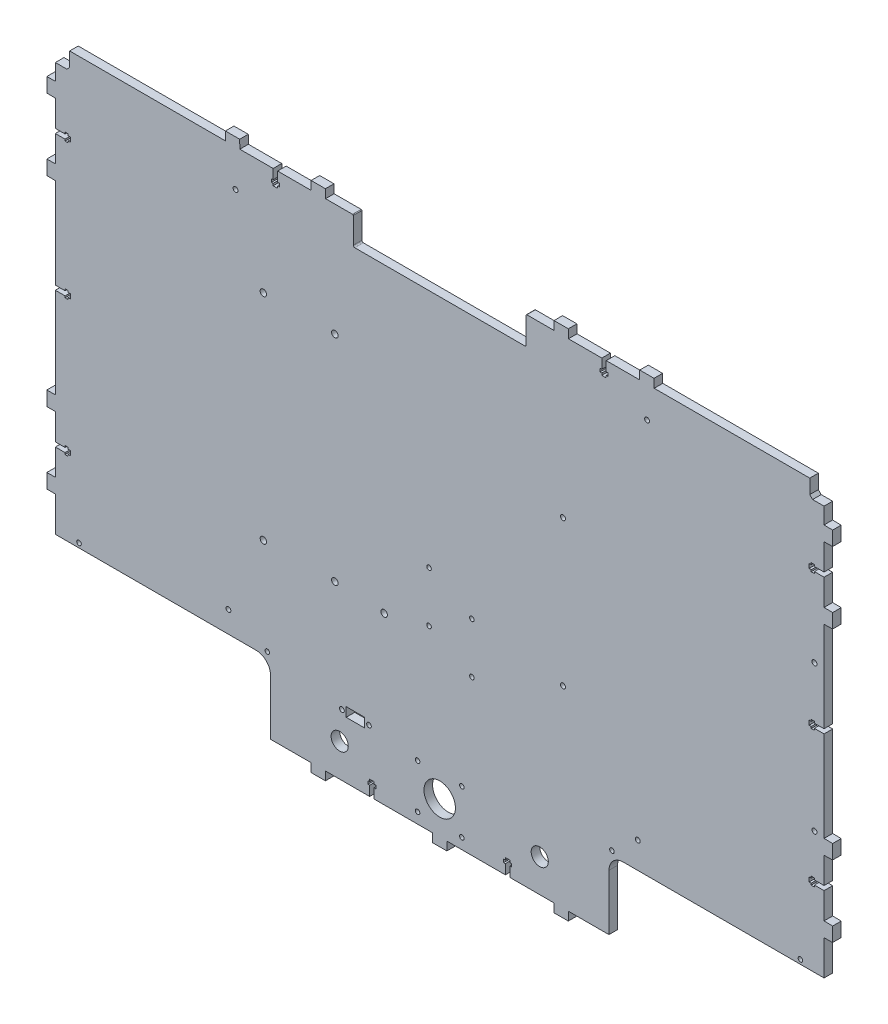
SolidWorks part; units mm, degrees
material "Клен"
ref_plane "Front" through (0, 0, 0) normal (0, 0, 1) x (1, 0, 0)
ref_plane "Top" through (0, 0, 0) normal (0, 1, 0) x (1, 0, 0)
ref_plane "Right" through (0, 0, 0) normal (1, 0, 0) x (0, 0, -1)
sketch "Эскиз1" plane through (0, 0, 0) normal (0, 0, 1) x (1, 0, 0)
  line L0 (89.7419, 501.6876) -> (118.0919, 501.6876)
  line L1 (118.0919, 501.6876) -> (118.1919, 495.6876)
  line L2 (118.1919, 495.6876) -> (128.1919, 495.6876)
  line L3 (128.1919, 495.6876) -> (128.2919, 501.6876)
  line L4 (128.2919, 501.6876) -> (159.1419, 501.6876)
  line L5 (159.1419, 501.6876) -> (159.1419, 508.4876)
  line L6 (159.1419, 508.4876) -> (157.9419, 508.4876)
  line L7 (157.9419, 508.4876) -> (157.9419, 510.6876)
  line L8 (157.9419, 510.6876) -> (159.1419, 510.6876)
  line L9 (159.1419, 510.6876) -> (159.1419, 512.1876)
  line L10 (159.1419, 512.1876) -> (162.2419, 512.1876)
  line L11 (162.2419, 512.1876) -> (162.2419, 510.6876)
  line L12 (162.2419, 510.6876) -> (163.4419, 510.6876)
  line L13 (163.4419, 510.6876) -> (163.4419, 508.4876)
  line L14 (163.4419, 508.4876) -> (162.2419, 508.4876)
  line L15 (162.2419, 508.4876) -> (162.2419, 501.6876)
  line L16 (-51.8081, 697.342) -> (-54.0081, 697.342)
  line L17 (-66.8081, 625.092) -> (-60.8081, 624.992)
  line L18 (162.2419, 501.6876) -> (203.0919, 501.6876)
  line L19 (203.0919, 501.6876) -> (203.1919, 495.6876)
  line L20 (203.1919, 495.6876) -> (213.1919, 495.6876)
  line L21 (213.1919, 495.6876) -> (213.2919, 501.6876)
  line L22 (213.2919, 501.6876) -> (254.1419, 501.6876)
  line L23 (254.1419, 501.6876) -> (254.1419, 508.4876)
  line L24 (254.1419, 508.4876) -> (252.9419, 508.4876)
  line L25 (252.9419, 508.4876) -> (252.9419, 510.6876)
  line L26 (252.9419, 510.6876) -> (254.1419, 510.6876)
  line L27 (254.1419, 510.6876) -> (254.1419, 512.1876)
  line L28 (254.1419, 512.1876) -> (257.2419, 512.1876)
  line L29 (257.2419, 512.1876) -> (257.2419, 510.6876)
  line L30 (257.2419, 510.6876) -> (258.4419, 510.6876)
  line L31 (258.4419, 510.6876) -> (258.4419, 508.4876)
  line L32 (258.4419, 508.4876) -> (257.2419, 508.4876)
  line L33 (257.2419, 508.4876) -> (257.2419, 501.6876)
  line L34 (257.2419, 501.6876) -> (288.0919, 501.6876)
  line L35 (288.0919, 501.6876) -> (288.1919, 495.6876)
  line L36 (288.1919, 495.6876) -> (298.1919, 495.6876)
  line L37 (298.1919, 495.6876) -> (298.2919, 501.6876)
  line L38 (298.2919, 501.6876) -> (326.6419, 501.6876)
  line L97 (367.1919, 848.6876) -> (358.2919, 848.6876)
  line L98 (358.2919, 848.6876) -> (358.1919, 854.6876)
  line L99 (358.1919, 854.6876) -> (348.1919, 854.6876)
  line L100 (348.1919, 854.6876) -> (348.0919, 848.6876)
  line L101 (348.0919, 848.6876) -> (324.7419, 848.6876)
  line L102 (324.7419, 848.6876) -> (324.7419, 841.8876)
  line L103 (324.7419, 841.8876) -> (325.9419, 841.8876)
  line L104 (325.9419, 841.8876) -> (325.9419, 839.6876)
  line L105 (325.9419, 839.6876) -> (324.7419, 839.6876)
  line L106 (324.7419, 839.6876) -> (324.7419, 838.1876)
  line L107 (324.7419, 838.1876) -> (321.6419, 838.1876)
  line L108 (321.6419, 838.1876) -> (321.6419, 839.6876)
  line L109 (321.6419, 839.6876) -> (320.4419, 839.6876)
  line L110 (320.4419, 839.6876) -> (320.4419, 841.8876)
  line L111 (320.4419, 841.8876) -> (321.6419, 841.8876)
  line L112 (321.6419, 841.8876) -> (321.6419, 848.6876)
  line L113 (321.6419, 848.6876) -> (298.2919, 848.6876)
  line L114 (298.2919, 848.6876) -> (298.1919, 854.6876)
  line L115 (298.1919, 854.6876) -> (288.1919, 854.6876)
  line L116 (288.1919, 854.6876) -> (288.0919, 848.6876)
  line L117 (288.0919, 848.6876) -> (269.1919, 848.6876)
  line L118 (268.6919, 848.1876) -> (268.6919, 830.092)
  line L119 (267.6919, 829.092) -> (148.6919, 829.092)
  line L120 (147.6919, 830.092) -> (147.6919, 848.092)
  line L121 (147.1919, 848.592) -> (128.2919, 848.592)
  line L122 (128.2919, 848.592) -> (128.1919, 854.592)
  line L123 (128.1919, 854.592) -> (118.1919, 854.592)
  line L124 (118.1919, 854.592) -> (118.0919, 848.592)
  line L125 (118.0919, 848.592) -> (94.7419, 848.592)
  line L126 (94.7419, 848.592) -> (94.7419, 841.792)
  line L127 (94.7419, 841.792) -> (95.9419, 841.792)
  line L128 (95.9419, 841.792) -> (95.9419, 839.592)
  line L129 (95.9419, 839.592) -> (94.7419, 839.592)
  line L130 (94.7419, 839.592) -> (94.7419, 838.092)
  line L131 (94.7419, 838.092) -> (91.6419, 838.092)
  line L132 (91.6419, 838.092) -> (91.6419, 839.592)
  line L133 (91.6419, 839.592) -> (90.4419, 839.592)
  line L134 (90.4419, 839.592) -> (90.4419, 841.792)
  line L135 (90.4419, 841.792) -> (91.6419, 841.792)
  line L136 (91.6419, 841.792) -> (91.6419, 848.592)
  line L137 (91.6419, 848.592) -> (68.2919, 848.592)
  line L138 (68.2919, 848.592) -> (68.1919, 854.592)
  line L139 (68.1919, 854.592) -> (58.1919, 854.592)
  line L140 (58.1919, 854.592) -> (58.0919, 848.592)
  line L141 (58.0919, 848.592) -> (49.1919, 848.592)
  line L199 (39.1919, 871.432) -> (39.1919, 501.6876) construction
  line L201 (142.7002, 547.9475) -> (155.7002, 547.9475)
  line L202 (155.7002, 547.9475) -> (155.7002, 541.4475)
  line L203 (155.7002, 541.4475) -> (142.7002, 541.4475)
  line L204 (142.7002, 541.4475) -> (142.7002, 547.9475)
  line L205 (-60.8081, 871.432) -> (-60.8081, 501.6876) construction
  line L206 (-50.3081, 793.542) -> (-51.8081, 793.542)
  line L207 (-60.8081, 698.542) -> (-60.8081, 635.192)
  line L208 (-60.8081, 796.642) -> (-54.0081, 796.642)
  line L209 (-51.8081, 793.542) -> (-51.8081, 792.342)
  line L210 (-54.0081, 701.642) -> (-54.0081, 702.842)
  line L211 (-51.8081, 701.642) -> (-50.3081, 701.642)
  line L212 (-60.8081, 836.592) -> (-60.8081, 825.192)
  line L213 (-51.8081, 796.642) -> (-50.3081, 796.642)
  line L214 (-54.0081, 702.842) -> (-51.8081, 702.842)
  line L215 (-50.3081, 698.542) -> (-51.8081, 698.542)
  line L216 (-54.0081, 603.542) -> (-60.8081, 603.542)
  line L217 (-60.8081, 775.192) -> (-66.8081, 775.092)
  line L218 (-50.3081, 603.542) -> (-51.8081, 603.542)
  line L219 (-60.8081, 814.992) -> (-60.8081, 796.642)
  line L220 (-54.0081, 796.642) -> (-54.0081, 797.842)
  line L221 (-54.0081, 797.842) -> (-51.8081, 797.842)
  line L222 (-51.8081, 698.542) -> (-51.8081, 697.342)
  line L223 (-54.0081, 607.842) -> (-51.8081, 607.842)
  line L224 (-60.8081, 574.992) -> (-60.8081, 550.592)
  line L225 (-52.8081, 836.592) -> (-60.8081, 836.592)
  line L226 (-54.0081, 792.342) -> (-54.0081, 793.542)
  line L227 (-51.8081, 606.642) -> (-50.3081, 606.642)
  line L228 (-66.8081, 585.092) -> (-66.8081, 575.092)
  line L229 (-51.8081, 792.342) -> (-54.0081, 792.342)
  line L230 (-54.0081, 606.642) -> (-54.0081, 607.842)
  line L231 (-51.8081, 603.542) -> (-51.8081, 602.342)
  line L232 (-66.8081, 825.092) -> (-66.8081, 815.092)
  line L233 (-50.3081, 796.642) -> (-50.3081, 793.542)
  line L234 (-60.8081, 635.192) -> (-66.8081, 635.092)
  line L235 (-60.8081, 585.192) -> (-66.8081, 585.092)
  line L236 (-66.8081, 815.092) -> (-60.8081, 814.992)
  line L237 (-66.8081, 775.092) -> (-66.8081, 765.092)
  line L238 (-51.8081, 602.342) -> (-54.0081, 602.342)
  line L239 (-66.8081, 765.092) -> (-60.8081, 764.992)
  line L240 (-50.3081, 701.642) -> (-50.3081, 698.542)
  line L241 (-60.8081, 624.992) -> (-60.8081, 606.642)
  line L243 (-54.0081, 793.542) -> (-60.8081, 793.542)
  line L244 (-54.0081, 697.342) -> (-54.0081, 698.542)
  line L245 (-60.8081, 825.192) -> (-66.8081, 825.092)
  line L246 (-51.8081, 797.842) -> (-51.8081, 796.642)
  line L247 (-51.8081, 702.842) -> (-51.8081, 701.642)
  line L248 (-60.8081, 603.542) -> (-60.8081, 585.192)
  line L249 (-54.0081, 698.542) -> (-60.8081, 698.542)
  line L250 (-66.8081, 635.092) -> (-66.8081, 625.092)
  line L251 (-60.8081, 764.992) -> (-60.8081, 701.642)
  line L252 (-54.0081, 602.342) -> (-54.0081, 603.542)
  line L254 (-50.8081, 848.592) -> (-50.8081, 838.592)
  line L255 (-50.8081, 838.592) -> (-52.8081, 836.592)
  line L256 (-60.8081, 701.642) -> (-54.0081, 701.642)
  line L257 (-60.8081, 606.642) -> (-54.0081, 606.642)
  line L258 (-50.3081, 606.642) -> (-50.3081, 603.542)
  line L259 (-60.8081, 793.542) -> (-60.8081, 775.192)
  line L260 (-51.8081, 607.842) -> (-51.8081, 606.642)
  line L261 (-66.8081, 575.092) -> (-60.8081, 574.992)
  line L263 (-50.8081, 848.592) -> (49.1919, 848.592)
  line L264 (377.1919, 871.432) -> (377.1919, 476.2445) construction
  line L265 (477.1919, 871.432) -> (477.1919, 476.2445) construction
  line L266 (477.1919, 625.0876) -> (483.1919, 625.1876)
  line L267 (466.6919, 698.6376) -> (466.6919, 701.7376)
  line L268 (477.1919, 550.6876) -> (477.1919, 575.0876)
  line L269 (470.3919, 701.7376) -> (477.1919, 701.7376)
  line L270 (477.1919, 585.2876) -> (477.1919, 603.6376)
  line L271 (477.1919, 796.7376) -> (477.1919, 815.0876)
  line L272 (477.1919, 575.0876) -> (483.1919, 575.1876)
  line L273 (468.1919, 603.6376) -> (466.6919, 603.6376)
  line L274 (477.1919, 635.2876) -> (477.1919, 698.6376)
  line L275 (470.3919, 792.4376) -> (468.1919, 792.4376)
  line L276 (467.1919, 838.6876) -> (467.1919, 848.6876)
  line L277 (483.1919, 635.1876) -> (477.1919, 635.2876)
  line L278 (468.1919, 796.7376) -> (468.1919, 797.9376)
  line L279 (483.1919, 585.1876) -> (477.1919, 585.2876)
  line L280 (468.1919, 698.6376) -> (466.6919, 698.6376)
  line L281 (468.1919, 793.6376) -> (466.6919, 793.6376)
  line L282 (469.1919, 836.6876) -> (467.1919, 838.6876)
  line L283 (483.1919, 575.1876) -> (483.1919, 585.1876)
  line L284 (470.3919, 603.6376) -> (470.3919, 602.4376)
  line L285 (470.3919, 697.4376) -> (468.1919, 697.4376)
  line L286 (477.1919, 701.7376) -> (477.1919, 765.0876)
  line L287 (477.1919, 793.6376) -> (470.3919, 793.6376)
  line L288 (483.1919, 815.1876) -> (483.1919, 825.1876)
  line L289 (470.3919, 606.7376) -> (477.1919, 606.7376)
  line L290 (470.3919, 698.6376) -> (470.3919, 697.4376)
  line L291 (483.1919, 775.1876) -> (477.1919, 775.2876)
  line L292 (466.6919, 603.6376) -> (466.6919, 606.7376)
  line L293 (466.6919, 793.6376) -> (466.6919, 796.7376)
  line L294 (470.3919, 797.9376) -> (470.3919, 796.7376)
  line L295 (477.1919, 825.2876) -> (477.1919, 836.6876)
  line L296 (470.3919, 602.4376) -> (468.1919, 602.4376)
  line L297 (483.1919, 625.1876) -> (483.1919, 635.1876)
  line L298 (468.1919, 697.4376) -> (468.1919, 698.6376)
  line L299 (470.3919, 702.9376) -> (470.3919, 701.7376)
  line L301 (468.1919, 607.9376) -> (470.3919, 607.9376)
  line L302 (470.3919, 793.6376) -> (470.3919, 792.4376)
  line L303 (466.6919, 796.7376) -> (468.1919, 796.7376)
  line L304 (477.1919, 603.6376) -> (470.3919, 603.6376)
  line L305 (477.1919, 606.7376) -> (477.1919, 625.0876)
  line L306 (477.1919, 775.2876) -> (477.1919, 793.6376)
  line L307 (468.1919, 792.4376) -> (468.1919, 793.6376)
  line L308 (477.1919, 815.0876) -> (483.1919, 815.1876)
  line L309 (466.6919, 606.7376) -> (468.1919, 606.7376)
  line L310 (468.1919, 606.7376) -> (468.1919, 607.9376)
  line L311 (466.6919, 701.7376) -> (468.1919, 701.7376)
  line L312 (468.1919, 702.9376) -> (470.3919, 702.9376)
  line L313 (468.1919, 797.9376) -> (470.3919, 797.9376)
  line L315 (470.3919, 607.9376) -> (470.3919, 606.7376)
  line L316 (477.1919, 698.6376) -> (470.3919, 698.6376)
  line L317 (468.1919, 701.7376) -> (468.1919, 702.9376)
  line L318 (477.1919, 765.0876) -> (483.1919, 765.1876)
  line L319 (470.3919, 796.7376) -> (477.1919, 796.7376)
  line L320 (468.1919, 602.4376) -> (468.1919, 603.6376)
  line L321 (483.1919, 765.1876) -> (483.1919, 775.1876)
  line L322 (483.1919, 825.1876) -> (477.1919, 825.2876)
  line L323 (477.1919, 836.6876) -> (469.1919, 836.6876)
  line L325 (367.1919, 848.6876) -> (467.1919, 848.6876)
  line L326 (336.6419, 550.6876) -> (377.1919, 550.6876)
  line L327 (326.6419, 501.6876) -> (326.6419, 540.6876)
  line L328 (377.1919, 550.6876) -> (477.1919, 550.6876)
  line L329 (89.7419, 540.592) -> (89.7419, 501.6876)
  line L330 (79.7419, 550.592) -> (39.1919, 550.592)
  line L331 (-60.8081, 550.592) -> (39.1919, 550.592)
  line L332 (208.1919, 486.1481) -> (208.1919, 880.8098) construction
  line L333 (107.749, 553.6876) -> (-66.0548, 553.6876) construction
  line L334 (315.5919, 553.6876) -> (489.3697, 553.6876) construction
  line L335 (87.5419, 557.9345) -> (87.5419, 540.5243) construction
  line L336 (328.7419, 492.2341) -> (328.7419, 562.4741) construction
  circle A0 centre (138.1919, 524.6876) radius 6
  circle A1 centre (208.1919, 524.6876) radius 11
  circle A2 centre (278.1919, 524.6876) radius 6
  circle A3 centre (192.6919, 540.1876) radius 1.6
  circle A4 centre (223.6919, 540.1876) radius 1.6
  circle A5 centre (158.7002, 544.6975) radius 1.6265
  circle A6 centre (139.7002, 544.6975) radius 1.7
  circle A7 centre (192.6919, 509.1876) radius 1.6
  circle A8 centre (223.6919, 509.1876) radius 1.6
  circle A9 centre (65.2801, 822.6887) radius 1.7
  circle A10 centre (353.3431, 826.9394) radius 1.7
  circle A11 centre (84.7857, 769.7888) radius 2.25
  circle A12 centre (134.7857, 769.7888) radius 2.25
  circle A13 centre (294.4853, 738.3683) radius 1.75
  circle A15 centre (200.7177, 661.1578) radius 1.6
  circle A16 centre (230.7177, 645.1578) radius 1.6
  circle A17 centre (200.7177, 625.8978) radius 1.6
  circle A18 centre (84.7857, 619.7888) radius 2.25
  circle A19 centre (134.7857, 619.7888) radius 2.25
  circle A20 centre (169.2857, 617.7888) radius 2.25
  circle A21 centre (230.7177, 609.8978) radius 1.6
  circle A22 centre (294.4853, 636.3683) radius 1.75
  circle A24 centre (346.7847, 569.0716) radius 1.7
  circle A26 centre (60.3069, 565.6434) radius 1.7
  arc A30 (148.6919, 829.092) -> (147.6919, 830.092) centre (148.6919, 830.092) cw
  arc A31 (268.6919, 830.092) -> (267.6919, 829.092) centre (267.6919, 830.092) cw
  arc A32 (269.1919, 848.6876) -> (268.6919, 848.1876) centre (269.1919, 848.1876) ccw
  arc A33 (147.6919, 848.092) -> (147.1919, 848.592) centre (147.1919, 848.092) ccw
  circle A36 centre (470.4853, 738.3683) radius 1.75
  circle A37 centre (470.4853, 636.3683) radius 1.75
  arc A38 (326.6419, 540.6876) -> (336.6419, 550.6876) centre (336.6419, 540.6876) cw
  arc A39 (89.7419, 540.592) -> (79.7419, 550.592) centre (79.7419, 540.592) ccw
  circle A40 centre (-44.2581, 553.6876) radius 1.6
  circle A41 centre (460.6419, 553.6876) radius 1.6
  circle A46 centre (87.5419, 553.6876) radius 1.6
  circle A47 centre (328.7419, 553.6876) radius 1.6
  dimension "D1" = 12
  dimension "D2" = 22
  dimension "D3" = 12
  dimension "D4" = 169
  dimension "D5" = 1
  dimension "D6" = 0.5
  dimension "D10" = 3.2
  dimension "D12" = 3.2
  dimension "D13" = 16.55
  dimension "D14" = 48.35
  dimension "D15" = 3.2
  dimension "D17" = 3.2
  dimension "D7" = 100
  dimension "D8" = 100
  dimension "D9" = 169
  dimension "D11" = 16.55
  dimension "D16" = 48.45
extrude "Бобышка-Вытянуть1" add sketch "Эскиз1" along normal blind 6 contours L0 L1 L2 L3 L4 L5 L6 L7 L8 L9 L10 L11 L12 L13 L14 L15 L18 L19 L20 L21 L22 L23 L24 L25 L26 L27 L28 L29 L30 L31 L32 L33 L34 L35 L36 L37 L38 region at (208.2304, 686.3762, 0)
